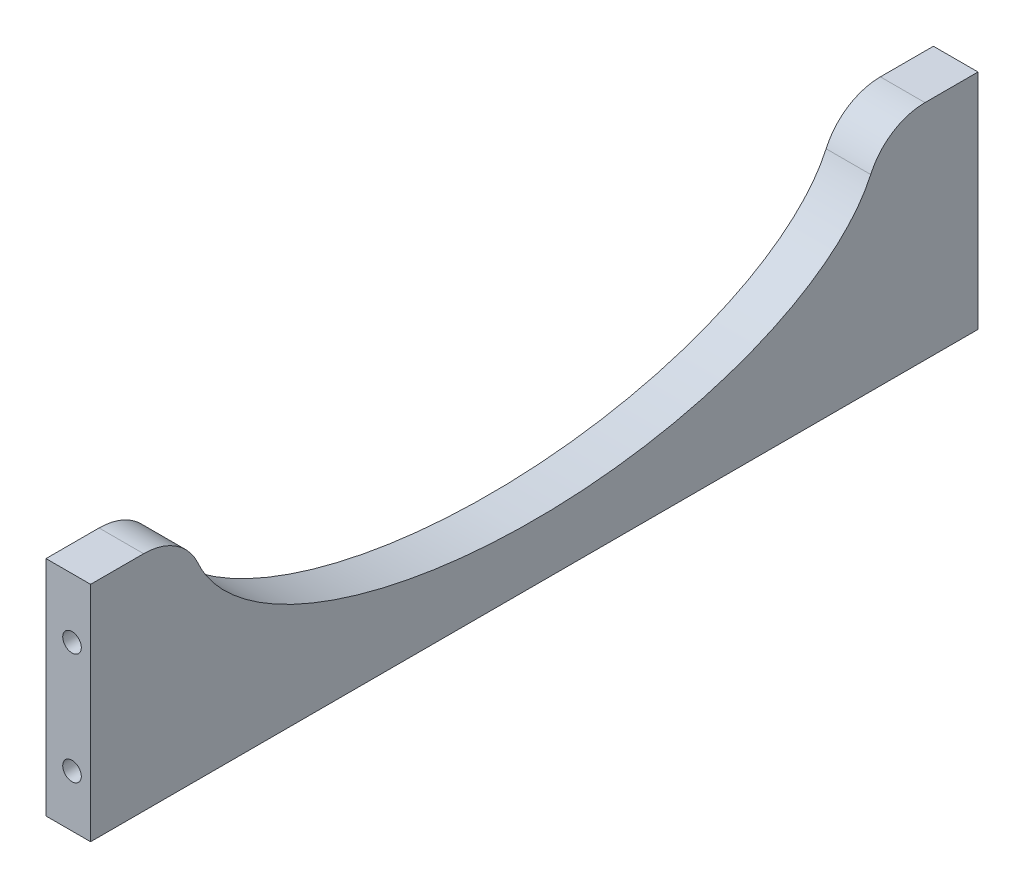
SolidWorks part; units mm, degrees
ref_plane "Front Plane" through (0, 0, 0) normal (0, 0, 1) x (1, 0, 0)
ref_plane "Top Plane" through (0, 0, 0) normal (0, 1, 0) x (1, 0, 0)
ref_plane "Right Plane" through (0, 0, 0) normal (1, 0, 0) x (0, 0, -1)
other "Configuration Table"
sketch "草图3" plane through (0, 0, 0) normal (0, 0, 1) x (1, 0, 0)
  line L1 (-77.4, 30) -> (-83.4, 30)
  line L2 (-83.4, 64.3) -> (-83.4, 0) construction
  line L3 (-83.4, 30) -> (-83.4, 0)
  line L4 (-83.4, 0) -> (-77.4, 0)
  line L5 (0, 0) -> (-82.1647, 0) construction
  line L6 (-83.4, 0) -> (-77.4, 0) construction
  line L7 (-77.4, 0) -> (-77.4, 30)
extrude "凸台-拉伸1" add sketch "草图3" along normal up to surface (119.4 mm away)
sketch "草图4" plane through (-83.4, 0, 0) normal (-1, 0, 0) x (0, 0, 1)
  line L0 (119.4, 30) -> (0, 30) construction
  ellipse E0 centre (59.7, 30) end of major axis (106.0102, 30) minor radius 22.3662
extrude "切除-拉伸1" cut sketch "草图4" against normal through all
fillet "圆角1" radius 8 2 edges at (-80.4, 30, 106.0102) (-80.4, 30, 13.3898)
sketch "草图5" plane through (0, 0, 119.4) normal (0, 0, 1) x (1, 0, 0)
  circle A0 centre (-79.9, 22) radius 1.25
  circle A1 centre (-79.9, 7) radius 1.25
extrude "切除-拉伸2" cut sketch "草图5" against normal blind 10
sketch "草图6" plane through (0, 0, 0) normal (0, 0, -1) x (-1, 0, 0)
  circle A0 centre (79.9, 22) radius 1.25
  circle A1 centre (79.9, 7) radius 1.25
extrude "切除-拉伸3" cut sketch "草图6" against normal blind 10
